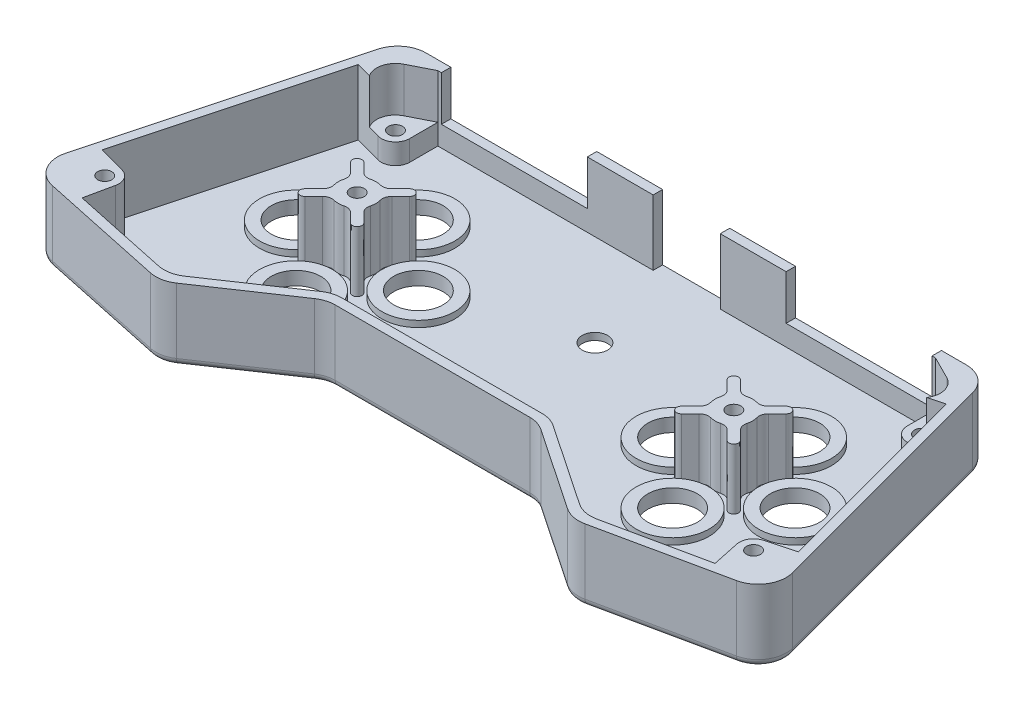
SolidWorks part; units mm, degrees
ref_plane "Front Plane" through (0, 0, 0) normal (0, 0, 1) x (1, 0, 0)
ref_plane "Top Plane" through (0, 0, 0) normal (0, 1, 0) x (1, 0, 0)
ref_plane "Right Plane" through (0, 0, 0) normal (1, 0, 0) x (0, 0, -1)
sketch "Sketch10" plane through (0, 0, 0) normal (0, 1, 0) x (1, 0, 0)
  line L0 (62, 32) -> (-62, 32)
  line L1 (-62, 32) -> (-78.8232, -30.7852)
  line L2 (-78.8232, -30.7852) -> (-43.6451, -38.2625)
  line L3 (-43.6451, -38.2625) -> (-22.5, -24)
  line L4 (-22.5, -24) -> (22.5, -24)
  line L5 (22.5, -24) -> (43.6451, -38.2625)
  line L6 (43.6451, -38.2625) -> (78.8232, -30.7852)
  line L7 (78.8232, -30.7852) -> (62, 32)
  line L8 (40, 13) -> (40, -13) construction
  line L9 (27, 0) -> (53, 0) construction
  line L10 (-40, 13) -> (-40, -13) construction
  line L11 (-53, 0) -> (-27, 0) construction
  line L12 (-27, 0) -> (27, 0) construction
  line L13 (0, 0) -> (0, 32) construction
  line L14 (0, 0) -> (0, -24) construction
  line L15 (78.8232, -30.7852) -> (22.5, -24) construction
  line L16 (-22.5, -24) -> (-78.8232, -30.7852) construction
  circle A0 centre (40, 13) radius 5.25
  circle A1 centre (27, 0) radius 5.25
  circle A2 centre (40, -13) radius 5.25
  circle A3 centre (53, 0) radius 5.25
  circle A4 centre (-40, 13) radius 5.25
  circle A5 centre (-53, 0) radius 5.25
  circle A6 centre (-40, -13) radius 5.25
  circle A7 centre (-27, 0) radius 5.25
  point P16 (40, 0)
  point P17 (-40, 0)
  dimension "D1" = 10.5
  dimension "D2" = 26
  dimension "D3" = 65
  dimension "D4" = 124
  dimension "D5" = 80
  dimension "D6" = 105
  dimension "D7" = 56
  dimension "D8" = 45
  dimension "D9" = 32
  dimension "D10" = 12
  dimension "D11" = 34
extrude "Boss-Extrude5" add sketch "Sketch10" along normal blind 1.5 separate body
sketch "Sketch11" plane through (0, 1.5, 0) normal (0, 1, 0) x (1, 0, 0)
  line L0 (-78.8232, -30.7852) -> (-62, 32)
  line L1 (-62, 32) -> (62, 32)
  line L2 (62, 32) -> (78.8232, -30.7852)
  line L3 (78.8232, -30.7852) -> (43.6451, -38.2625)
  line L4 (43.6451, -38.2625) -> (22.5, -24)
  line L5 (22.5, -24) -> (-22.5, -24)
  line L6 (-22.5, -24) -> (-43.6451, -38.2625)
  line L7 (-43.6451, -38.2625) -> (-78.8232, -30.7852)
  line L8 (-44.0596, -36.1297) -> (-76.3459, -29.2671)
  line L9 (-76.3459, -29.2671) -> (-60.4653, 30)
  line L10 (-60.4653, 30) -> (60.4653, 30)
  line L11 (60.4653, 30) -> (76.3459, -29.2671)
  line L12 (76.3459, -29.2671) -> (44.0596, -36.1297)
  line L13 (44.0596, -36.1297) -> (23.1115, -22)
  line L14 (23.1115, -22) -> (-23.1115, -22)
  line L15 (-23.1115, -22) -> (-44.0596, -36.1297)
  dimension "D1" = 2
extrude "Boss-Extrude7" add sketch "Sketch11" along direction (0, -1, 0) on the side of the normal offset from surface (13.875 mm away) 15.375 up to face at (-40, 0, 18.25)
fillet "Fillet4" radius 6 16 edges at (62, 7.6875, -32) (78.8232, 7.6875, 30.7852) (43.6451, 7.6875, 38.2625) (22.5, 7.6875, 24) (-22.5, 7.6875, 24) (-43.6451, 7.6875, 38.2625) (-62, 7.6875, -32) (-78.8232, 7.6875, 30.7852) (76.3459, 8.4375, 29.2671) (60.4653, 8.4375, -30) (44.0596, 8.4375, 36.1297) (23.1115, 8.4375, 22) (-23.1115, 8.4375, 22) (-44.0596, 8.4375, 36.1297) (-76.3459, 8.4375, 29.2671) (-60.4653, 8.4375, -30)
fillet "Fillet5" radius 1.5 16 edges at (43.7439, 0, 37.7539) (32.7772, 0, 30.9321) (22.4198, 0, 24.2622) (0, 0, 24) (-22.4198, 0, 24.2622) (-32.7772, 0, 30.9321) (-43.7439, 0, 37.7539) (-59.3875, 0, 34.9164) (-76.5071, 0, 29.3658) (-70.1892, 0, -1.4375) (-61.0486, 0, -30.7601) (0, 0, -32) (61.0486, 0, -30.7601) (70.1892, 0, -1.4375) (76.5071, 0, 29.3658) (59.3875, 0, 34.9164)
sketch "Sketch12" plane through (0, 1.5, 0) normal (0, 1, 0) x (1, 0, 0)
  line L0 (-62.4334, 22.6551) -> (-56.6378, 21.1022)
  line L1 (-61.6569, 25.5529) -> (-74.7095, -23.1598) construction
  line L2 (-52.8614, 24) -> (-52.8614, 30)
  line L3 (55.8614, 30) -> (-55.8614, 30) construction
  line L4 (-52.8614, 30) -> (-55.8614, 30)
  line L5 (-61.6569, 25.5529) -> (-62.4334, 22.6551)
  line L6 (-74.7095, -23.1598) -> (-73.933, -20.2621)
  line L7 (-73.933, -20.2621) -> (-68.1375, -21.815)
  line L8 (-65.9795, -25.3365) -> (-67.227, -31.2054)
  line L9 (-70.1614, -30.5816) -> (-46.5508, -35.6002) construction
  line L10 (-67.227, -31.2054) -> (-70.1614, -30.5816)
  line L11 (0, 0) -> (0, 17.9434) construction
  line L12 (67.227, -31.2054) -> (70.1614, -30.5816)
  line L13 (65.9795, -25.3365) -> (67.227, -31.2054)
  line L14 (73.933, -20.2621) -> (68.1375, -21.815)
  line L15 (74.7095, -23.1598) -> (73.933, -20.2621)
  line L16 (61.6569, 25.5529) -> (62.4334, 22.6551)
  line L17 (52.8614, 30) -> (55.8614, 30)
  line L18 (52.8614, 24) -> (52.8614, 30)
  line L19 (62.4334, 22.6551) -> (56.6378, 21.1022)
  arc A0 (-56.6378, 21.1022) -> (-52.8614, 24) centre (-55.8614, 24) ccw
  arc A1 (-55.8614, 30) -> (-61.6569, 25.5529) centre (-55.8614, 24) ccw
  arc A2 (-68.1375, -21.815) -> (-65.9795, -25.3365) centre (-68.9139, -24.7127) cw
  arc A3 (-70.1614, -30.5816) -> (-74.7095, -23.1598) centre (-68.9139, -24.7127) cw
  circle A4 centre (-55.8614, 24) radius 1.5
  circle A5 centre (-68.9139, -24.7127) radius 1.5
  circle A6 centre (68.9139, -24.7127) radius 1.5
  circle A7 centre (55.8614, 24) radius 1.5
  arc A8 (70.1614, -30.5816) -> (74.7095, -23.1598) centre (68.9139, -24.7127) ccw
  arc A9 (68.1375, -21.815) -> (65.9795, -25.3365) centre (68.9139, -24.7127) ccw
  arc A10 (55.8614, 30) -> (61.6569, 25.5529) centre (55.8614, 24) cw
  arc A11 (56.6378, 21.1022) -> (52.8614, 24) centre (55.8614, 24) cw
  point P45 (-48.6255, -14.6469)
  point P46 (51.5726, -14.086)
  point P47 (0, 0)
  point P48 (0, 0)
  point P49 (0, 0)
  point P50 (0, 0)
  point P51 (-72.653, -15.4851)
  dimension "D1" = 3
  dimension "D2" = 1.5
extrude "Boss-Extrude8" add sketch "Sketch12" along normal up to surface (13.875 mm away) up to face at (0, 15.375, 14.2164)
sketch "Sketch14" plane through (0, 0, -30) normal (0, 0, 1) x (1, 0, 0)
  line L0 (-52.8614, 15.375) -> (52.8614, 15.375) construction
  line L1 (-52.1114, 15.375) -> (-21.1114, 15.375)
  line L2 (-52.1114, 15.375) -> (-52.1114, 5.875)
  line L3 (-52.1114, 5.875) -> (-21.1114, 5.875)
  line L4 (-21.1114, 15.375) -> (-21.1114, 5.875)
  line L5 (0, 0) -> (0, 15.375) construction
  line L6 (21.1114, 15.375) -> (21.1114, 5.875)
  line L7 (52.1114, 5.875) -> (21.1114, 5.875)
  line L8 (52.1114, 15.375) -> (52.1114, 5.875)
  line L9 (52.1114, 15.375) -> (21.1114, 15.375)
  line L10 (-6.625, 14.53) -> (-6.625, 2) construction
  line L11 (-7.125, 15.375) -> (7.125, 15.375)
  line L12 (-7.125, 15.375) -> (-7.125, 1.5)
  line L13 (-7.125, 1.5) -> (7.125, 1.5)
  line L14 (7.125, 15.375) -> (7.125, 1.5)
  line L15 (52.8614, 1.5) -> (-52.8614, 1.5) construction
  dimension "D1" = 0.5
  dimension "D2" = 9.5
  dimension "D3" = 0.75
  dimension "D4" = 31
extrude "Cut-Extrude2" cut sketch "Sketch14" against normal through all
sketch "Sketch13" plane through (0, 15.375, 0) normal (0, 1, 0) x (1, 0, 0)
  line L0 (-57.6668, 27.5694) -> (-52.8614, 30)
  line L1 (-52.8614, 30) -> (-51.9226, 24.6973)
  line L2 (57.6668, 27.5694) -> (52.8614, 30)
  line L3 (52.8614, 30) -> (51.9226, 24.6973)
  arc A0 (-57.6668, 27.5694) -> (-51.9226, 24.6973) centre (-55.8614, 24) ccw
  arc A1 (51.9226, 24.6973) -> (57.6668, 27.5694) centre (55.8614, 24) ccw
  dimension "D1" = 8
extrude "Cut-Extrude1" cut sketch "Sketch13" against normal up to surface (9.5 mm away) up to face at (-36.6114, 5.875, -31)
sketch "Sketch15" plane through (0, 0, 0) normal (0, -1, 0) x (1, 0, 0)
  line L0 (0, -10.5) -> (0, -30.5) construction
  line L1 (-57.396, -30.5) -> (57.396, -30.5) construction
  circle A0 centre (0, -10.5) radius 2.7
  dimension "D2" = 5.4
  dimension "D1" = 20
extrude "Cut-Extrude3" cut sketch "Sketch15" against normal through all contours A0
sketch "Sketch16" plane through (0, 1.5, 0) normal (0, 1, 0) x (1, 0, 0)
  circle A0 centre (-40, 13) radius 7.75
  circle A1 centre (-40, 13) radius 5.25
  circle A2 centre (-27, 0) radius 7.75
  circle A3 centre (-27, 0) radius 5.25
  circle A4 centre (-53, 0) radius 5.25
  circle A5 centre (-53, 0) radius 7.75
  circle A6 centre (-40, -13) radius 5.25
  circle A7 centre (-40, -13) radius 7.75
  circle A8 centre (-40, 13) radius 5.25 construction
  circle A9 centre (-53, 0) radius 5.25 construction
  circle A10 centre (-40, -13) radius 5.25 construction
  circle A11 centre (-27, 0) radius 5.25 construction
  dimension "D1" = 2.5
extrude "Boss-Extrude9" add sketch "Sketch16" along normal blind 1.35
sketch "Sketch17" plane through (0, 1.5, 0) normal (0, 1, 0) x (1, 0, 0)
  line L0 (-43.4457, 2.0315) -> (-46.2741, 4.8599)
  line L3 (-44.8599, 6.2741) -> (-42.0315, 3.4457)
  line L4 (-37.9685, 3.4457) -> (-35.1401, 6.2741)
  line L5 (-33.7259, 4.8599) -> (-36.5543, 2.0315)
  line L6 (-36.5543, -2.0315) -> (-33.7259, -4.8599)
  line L7 (-35.1401, -6.2741) -> (-37.9685, -3.4457)
  line L8 (-42.0315, -3.4457) -> (-44.8599, -6.2741)
  line L9 (-46.2741, -4.8599) -> (-43.4457, -2.0315)
  line L10 (-45.567, -5.567) -> (-40, 0) construction
  line L11 (-40, 0) -> (-34.433, 5.567) construction
  line L12 (-34.433, -5.567) -> (-40, 0) construction
  line L13 (-45.567, 5.567) -> (-40, 0) construction
  line L14 (-45.567, 5.567) -> (-34.433, 5.567) construction
  line L15 (-40, 0) -> (0, 0) construction
  arc A0 (-43.4457, 2.0315) -> (-43.4457, -2.0315) centre (-40, 0) ccw
  arc A3 (-46.2741, 4.8599) -> (-44.8599, 6.2741) centre (-45.567, 5.567) cw
  arc A4 (-35.1401, 6.2741) -> (-33.7259, 4.8599) centre (-34.433, 5.567) cw
  arc A5 (-33.7259, -4.8599) -> (-35.1401, -6.2741) centre (-34.433, -5.567) cw
  arc A6 (-44.8599, -6.2741) -> (-46.2741, -4.8599) centre (-45.567, -5.567) cw
  arc A7 (-37.9685, 3.4457) -> (-42.0315, 3.4457) centre (-40, 0) ccw
  arc A8 (-36.5543, -2.0315) -> (-36.5543, 2.0315) centre (-40, 0) ccw
  arc A9 (-42.0315, -3.4457) -> (-37.9685, -3.4457) centre (-40, 0) ccw
  circle A10 centre (-40, 0) radius 1.5
  dimension "D1" = 40
  dimension "D4" = 8
  dimension "D5" = 3
  dimension "D2" = 2
  dimension "D3" = 4
extrude "Boss-Extrude10" add sketch "Sketch17" along normal offset from surface (12.875 mm away) 1 up to face at (-14.1182, 15.375, -31)
fillet "Fillet6" radius 2 8 edges at (-43.4457, 7.9375, 2.0315) (-43.4457, 7.9375, -2.0315) (-42.0315, 7.9375, -3.4457) (-37.9685, 7.9375, -3.4457) (-36.5543, 7.9375, -2.0315) (-36.5543, 7.9375, 2.0315) (-37.9685, 7.9375, 3.4457) (-42.0315, 7.9375, 3.4457)
mirror "Mirror1" about plane through (0, 0, 0) normal (1, 0, 0) of "Fillet6", "Boss-Extrude9", "Boss-Extrude10"
